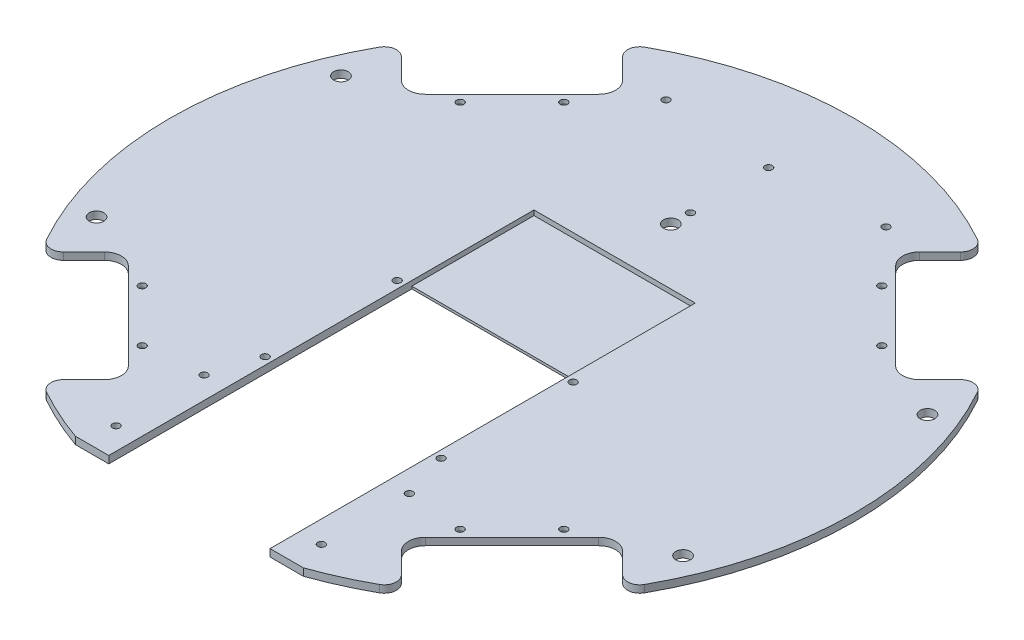
SolidWorks part; units mm, degrees
material "1060 Alloy"
ref_plane "Front Plane" through (0, 0, 0) normal (0, 0, 1) x (1, 0, 0)
ref_plane "Top Plane" through (0, 0, 0) normal (0, 1, 0) x (1, 0, 0)
ref_plane "Right Plane" through (0, 0, 0) normal (1, 0, 0) x (0, 0, -1)
sketch "Sketch1" plane through (0, 0, 0) normal (0, 1, 0) x (1, 0, 0)
  circle A0 centre (0, 0) radius 140
  dimension "D1" = 280
extrude "Boss-Extrude1" add sketch "Sketch1" along normal blind 3
sketch "Sketch7" plane through (0, 3, 0) normal (0, 1, 0) x (1, 0, 0)
  line L0 (-96.2019, -60.7758) -> (-60.7758, -96.2019)
  line L1 (-106.0307, -60.7758) -> (-121.6224, -76.3675)
  line L2 (-60.7758, -106.0307) -> (-76.3675, -121.6224)
  line L3 (-121.6224, -76.3675) -> (-76.3675, -121.6224)
  line L4 (0, 0) -> (-98.9949, -98.9949) construction
  line L7 (0, 0) -> (0, 130) construction
  circle A0 centre (0, 0) radius 140 construction
  arc A1 (-106.0307, -60.7758) -> (-96.2019, -60.7758) centre (-101.1163, -65.6902) cw
  arc A2 (-60.7758, -96.2019) -> (-60.7758, -106.0307) centre (-65.6902, -101.1163) cw
  dimension "D4" = 6.95
  dimension "D1" = 111
  dimension "D2" = 64
  dimension "D3" = 135
extrude "Cut-Extrude4" cut sketch "Sketch7" against normal up to next
sketch "Sketch9" plane through (0, 3, 0) normal (0, 1, 0) x (1, 0, 0)
  line L1 (-60.7758, -96.2019) -> (-96.2019, -60.7758) construction
  line L4 (-106.0307, -60.7758) -> (-119.0017, -73.7469) construction
  circle A0 centre (-86.267, -65.0538) radius 1.5
  circle A1 centre (-65.0538, -86.267) radius 1.5
  dimension "D4" = 3
  dimension "D1" = 4
  dimension "D2" = 30
  dimension "D3" = 17
  dimension "D5" = 4
extrude "Cut-Extrude6" cut sketch "Sketch9" against normal up to next
fillet "Fillet1" radius 5 2 edges at (-73.7469, 1.5, 119.0017) (-119.0017, 1.5, 73.7469)
pattern_circular "CirPattern1" count 4 over 360 about axis through (0, 3, 0) along (0, 1, 0) of "Cut-Extrude4", "Fillet1", "Cut-Extrude6"
sketch "Sketch2" plane through (0, 3, 0) normal (0, 1, 0) x (1, 0, 0)
  line L0 (-46.6476, -132) -> (-33, -132)
  line L1 (-33, -132) -> (-33, -8)
  line L2 (-33, -8) -> (33, -8)
  line L3 (33, -8) -> (33, -132)
  line L4 (33, -132) -> (46.6476, -132)
  line L5 (46.6476, -132) -> (46.6476, -140)
  line L6 (46.6476, -140) -> (-46.6476, -140)
  line L7 (-46.6476, -140) -> (-46.6476, -132)
  circle A0 centre (0, 0) radius 140 construction
  dimension "D1" = 8
  dimension "D2" = 124
  dimension "D3" = 66
  dimension "D4" = 13.6476
extrude "Cut-Extrude1" cut sketch "Sketch2" against normal up to next
fillet "Fillet3" radius 1.5 8 edges at (65.0538, 0, 87.767) (86.267, 0, 66.5538) (86.267, 0, -63.5538) (65.0538, 0, -84.767) (-65.0538, 0, -84.767) (-86.267, 0, -63.5538) (-65.0538, 0, 87.767) (-86.267, 0, 66.5538)
sketch "Sketch10" plane through (0, 3, 0) normal (0, 1, 0) x (1, 0, 0)
  circle A0 centre (-36, -65) radius 1.5
  circle A1 centre (36, -65) radius 1.5
  circle A2 centre (-36, -11) radius 1.5
  circle A3 centre (36, -11) radius 1.5
  dimension "D3" = 3
  dimension "D1" = 36
  dimension "D2" = 72
  dimension "D4" = 65
  dimension "D5" = 54
extrude "Cut-Extrude7" cut sketch "Sketch10" against normal up to next
sketch "Sketch13" plane through (0, 3, 0) normal (0, 1, 0) x (1, 0, 0)
  line L1 (-33, -132) -> (-46.6476, -132) construction
  circle A0 centre (-42, -84) radius 1.5
  circle A1 centre (-42, -120) radius 1.5
  circle A2 centre (42, -120) radius 1.5
  circle A3 centre (42, -84) radius 1.5
  dimension "D1" = 3
  dimension "D2" = 12
  dimension "D3" = 36
  dimension "D4" = 42
  dimension "D5" = 42
extrude "Cut-Extrude9" cut sketch "Sketch13" against normal up to next
sketch "Sketch16" plane through (0, 3, 0) normal (0, 1, 0) x (1, 0, 0)
  circle A0 centre (0, 73) radius 1.5
  circle A1 centre (-45, 108) radius 1.5
  circle A2 centre (45, 108) radius 1.5
  circle A3 centre (0, 105) radius 1.5
  circle A4 centre (0, 65) radius 3
  dimension "D2" = 3
  dimension "D5" = 6
  dimension "D1" = 73
  dimension "D3" = 108
  dimension "D4" = 90
  dimension "D6" = 32
  dimension "D7" = 65
extrude "Cut-Extrude12" cut sketch "Sketch16" against normal up to next
sketch "Sketch17" plane through (0, 3, 0) normal (0, 1, 0) x (1, 0, 0)
  circle A0 centre (-120, 50) radius 3
  circle A1 centre (-120, -50) radius 3
  circle A2 centre (120, 50) radius 3
  circle A3 centre (120, -50) radius 3
  dimension "D1" = 6
  dimension "D2" = 50
  dimension "D3" = 50
  dimension "D4" = 120
  dimension "D5" = 120
extrude "Cut-Extrude13" cut sketch "Sketch17" against normal up to next
sketch "Sketch18" plane through (0, 3, 0) normal (0, 1, 0) x (1, 0, 0)
  line L1 (-33, -8) -> (33, -8)
  line L2 (-33, -8) -> (-33, 42)
  line L3 (-33, 42) -> (33, 42)
  line L4 (33, -8) -> (33, 42)
  line L6 (33, -8) -> (-33, -8) construction
  line L7 (-33, -8) -> (-33, -132) construction
  dimension "D1" = 50
extrude "Cut-Extrude14" cut sketch "Sketch18" against normal blind 2
